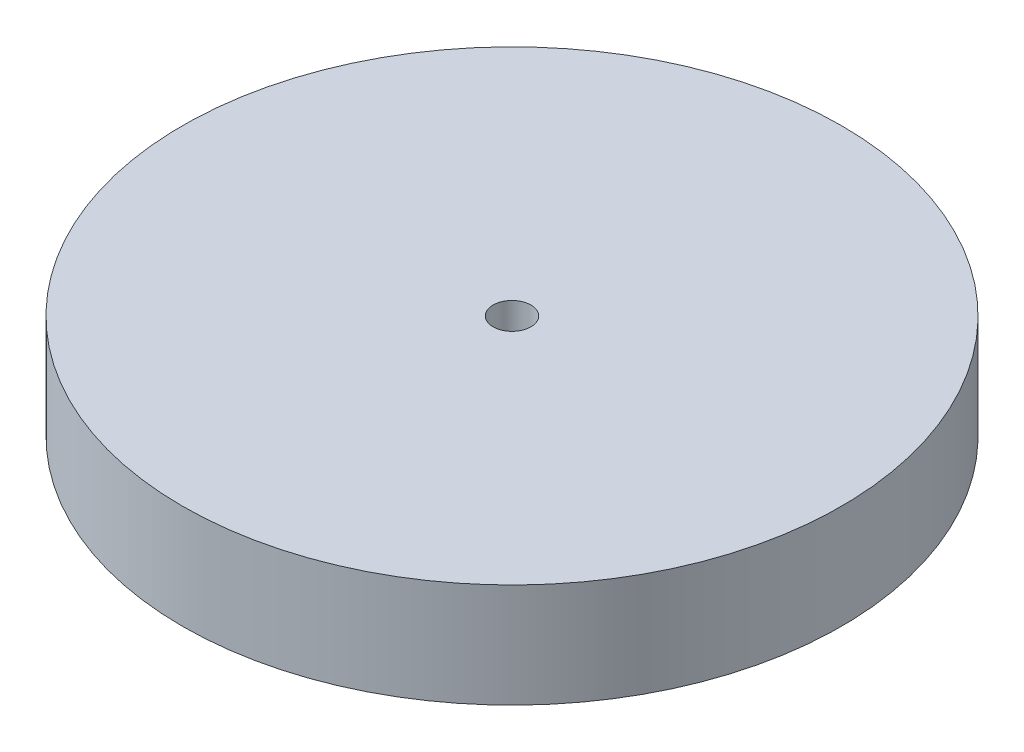
SolidWorks part; units mm, degrees
ref_plane "Front Plane" through (0, 0, 0) normal (0, 0, 1) x (1, 0, 0)
ref_plane "Top Plane" through (0, 0, 0) normal (0, 1, 0) x (1, 0, 0)
ref_plane "Right Plane" through (0, 0, 0) normal (1, 0, 0) x (0, 0, -1)
sketch "Sketch1" plane through (0, 0, 0) normal (0, 1, 0) x (1, 0, 0)
  circle A0 centre (0, 0) radius 60.325
  dimension "D1" = 120.65
extrude "Boss-Extrude1" add sketch "Sketch1" along normal blind 19.05
sketch "Sketch2" plane through (0, 0, 0) normal (0, -1, 0) x (1, 0, 0)
  circle A0 centre (0, 0) radius 57.15
  circle A1 centre (0, 0) radius 55.5625
  dimension "D1" = 114.3
  dimension "D2" = 111.125
extrude "Cut-Extrude1" cut sketch "Sketch2" against normal blind 3.175
sketch "Sketch3" plane through (0, 0, 0) normal (0, -1, 0) x (1, 0, 0)
  line L1 (-4.8486, 3.4631) -> (4.8486, 3.4631)
  line L2 (-4.8486, 3.4631) -> (-4.8486, -3.4631)
  line L3 (-4.8486, -3.4631) -> (4.8486, -3.4631)
  line L4 (4.8486, 3.4631) -> (4.8486, -3.4631)
  line L5 (-4.8486, 3.4631) -> (4.8486, -3.4631) construction
  line L6 (-4.8486, -3.4631) -> (4.8486, 3.4631) construction
  point P0 (0, 0)
extrude "Cut-Extrude2" cut sketch "Sketch3" against normal blind 2.54
sketch "Sketch4" plane through (0, 0, 0) normal (0, -1, 0) x (1, 0, 0)
  circle A0 centre (0, 0) radius 3.4631
extrude "Cut-Extrude3" cut sketch "Sketch4" against normal through all
